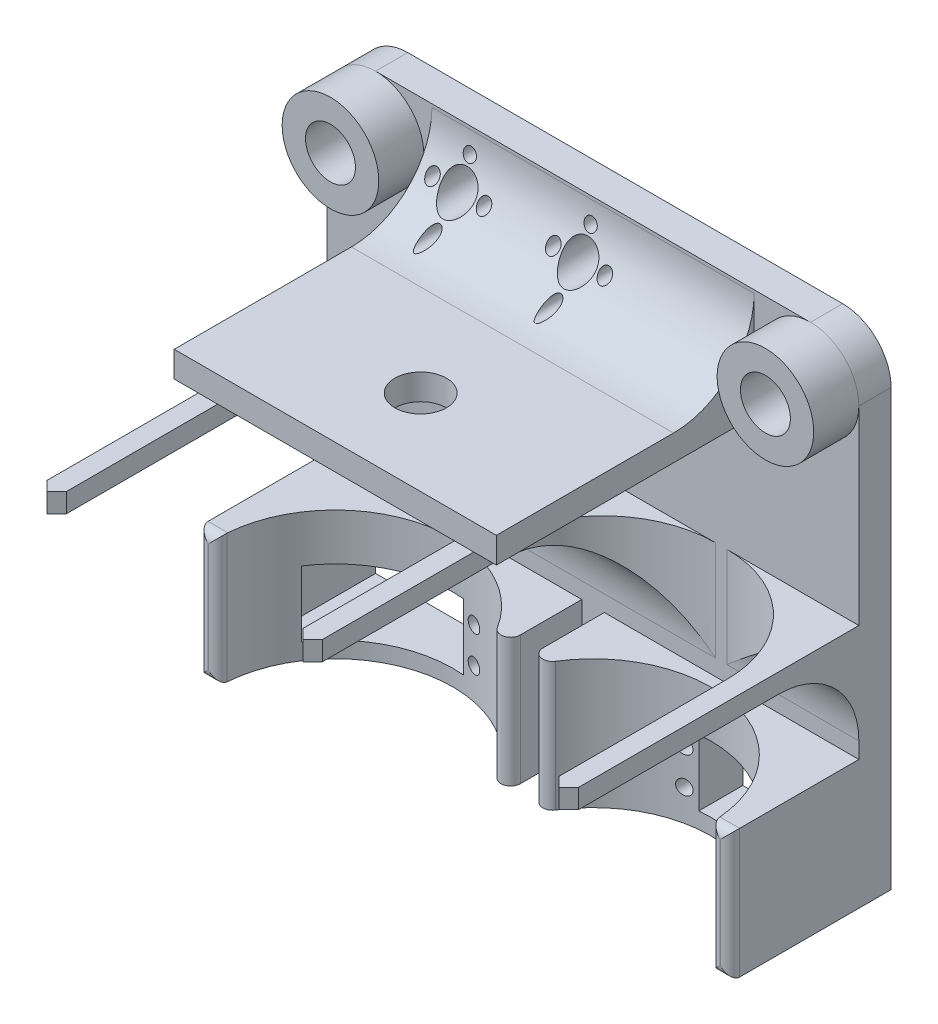
SolidWorks part; units mm, degrees
ref_plane "Plan de face" through (0, 0, 0) normal (0, 0, 1) x (1, 0, 0)
ref_plane "Plan de dessus" through (0, 0, 0) normal (0, 1, 0) x (1, 0, 0)
ref_plane "Plan de droite" through (0, 0, 0) normal (1, 0, 0) x (0, 0, -1)
sketch "Esquisse1" plane through (0, 0, 0) normal (0, 0, 1) x (1, 0, 0)
  line L1 (-82.5, -75) -> (82.5, -75)
  line L2 (-82.5, -75) -> (-82.5, 75)
  line L3 (-82.5, 75) -> (82.5, 75)
  line L4 (82.5, -75) -> (82.5, 75)
  line L5 (-82.5, -75) -> (82.5, 75) construction
  line L6 (-82.5, 75) -> (82.5, -75) construction
  point P0 (0, 0)
  dimension "D1" = 165
  dimension "D2" = 150
extrude "Boss.-Extru.1" add sketch "Esquisse1" along normal blind 10
sketch "Esquisse2" plane through (0, 0, 10) normal (0, 0, 1) x (1, 0, 0)
  line L0 (-82.5, 75) -> (-82.5, -75) construction
  line L1 (82.5, 75) -> (-82.5, 75) construction
  line L2 (0, -55) -> (0, 55) construction
  circle A0 centre (-67.5, 60) radius 7.75
  circle A2 centre (67.5, 60) radius 7.75
  dimension "D1" = 15.5
  dimension "D3" = 15
  dimension "D2" = 15
extrude "Enlèv. mat.-Extru.1" cut sketch "Esquisse2" against normal blind 10
sketch "Esquisse3" plane through (0, 0, 0) normal (0, 0, -1) x (-1, 0, 0)
  circle A0 centre (-67.5, 60) radius 15
  circle A1 centre (67.5, 60) radius 15
  circle A2 centre (-67.5, 60) radius 7.75
  circle A3 centre (67.5, 60) radius 7.75
  dimension "D1" = 30
  dimension "D2" = 30
extrude "Boss.-Extru.2" add sketch "Esquisse3" against normal blind 24
fillet "Congé1" radius 15 2 edges at (82.5, 75, 5) (-82.5, 75, 5)
sketch "Esquisse4" plane through (0, 0, 0) normal (0, 0, -1) x (-1, 0, 0)
  line L0 (-67.5, 75) -> (67.5, 75) construction
  line L1 (82.5, 60) -> (82.5, -75) construction
  circle A0 centre (0, 60) radius 5.25
  circle A1 centre (0, 60) radius 11
  circle A2 centre (0, 52) radius 2
  circle A3 centre (-8, 60) radius 2
  circle A4 centre (0, 68) radius 2
  circle A5 centre (8, 60) radius 2
  circle A6 centre (37.5, 60) radius 5.25
  circle A7 centre (37.5, 60) radius 11
  circle A8 centre (37.5, 52) radius 2
  circle A9 centre (29.5, 60) radius 2
  circle A10 centre (37.5, 68) radius 2
  circle A11 centre (45.5, 60) radius 2
  point P18 (0, 60)
  point P26 (37.5, 60)
  point P32 (42.5, 60)
  point P33 (37.5, 60)
  dimension "D1" = 10.5
  dimension "D2" = 15
  dimension "D3" = 10.5
  dimension "D4" = 22
  dimension "D5" = 4
  dimension "D6" = 8
  dimension "D8" = 22
  dimension "D9" = 4
  dimension "D10" = 8
  dimension "D11" = 45
  dimension "D12" = 15
  dimension "D7" = 4
  dimension "D13" = 4
extrude "Enlèv. mat.-Extru.2" cut sketch "Esquisse4" against normal blind 28 contours A6 | A9 | A10 | A11 | A8 | A2 | A5 | A4 | A3 | A0 region at (-37.5, 60, 0) region at (-37.5, 52, 0) region at (-29.5, 60, 0) region at (-37.5, 68, 0) region at (-45.5, 60, 0)
sketch "Esquisse6" plane through (0, -75, 0) normal (0, -1, 0) x (1, 0, 0)
  line L0 (-82.5, 10) -> (82.5, 10) construction
  line L2 (-76.5, 10) -> (-3.5, 10)
  line L3 (-3.5, 10) -> (-3.5, 50)
  line L4 (0, 0) -> (0, 41.8553) construction
  line L5 (3.5, 10) -> (3.5, 50)
  line L6 (76.5, 10) -> (3.5, 10)
  line L8 (-52.5, 10) -> (-82.5, 10) construction
  line L10 (-82.5, 10) -> (-82.5, 50)
  line L11 (-82.5, 50) -> (-76.5, 50)
  line L12 (-82.5, 10) -> (-76.5, 10)
  line L13 (76.5, 10) -> (82.5, 10)
  line L14 (82.5, 10) -> (82.5, 50)
  line L15 (82.5, 50) -> (76.5, 50)
  arc A0 (-76.5, 50) -> (-3.5, 50) centre (-40, 50) ccw
  arc A1 (76.5, 50) -> (3.5, 50) centre (40, 50) cw
  dimension "D1" = 36.5
  dimension "D2" = 73
  dimension "D3" = 40
  dimension "D4" = 6
extrude "Boss.-Extru.3" add sketch "Esquisse6" against normal blind 40
sketch "Esquisse5" plane through (0, 0, 0) normal (0, 0, -1) x (-1, 0, 0)
  line L0 (-82.5, -75) -> (-82.5, 60) construction
  line L1 (-77.5, -70) -> (-36.5, -70)
  line L2 (-77.5, -70) -> (-77.5, -49.5)
  line L3 (-77.5, -49.5) -> (-36.5, -49.5)
  line L4 (-36.5, -70) -> (-36.5, -49.5)
  line L5 (82.5, -75) -> (-82.5, -75) construction
  line L6 (0, 13.2) -> (0, -13.2) construction
  line L7 (36.5, -70) -> (36.5, -49.5)
  line L8 (77.5, -70) -> (36.5, -70)
  line L9 (77.5, -70) -> (77.5, -49.5)
  line L10 (77.5, -49.5) -> (36.5, -49.5)
  line L11 (-77.5, -59.75) -> (-36.5, -59.75) construction
  circle A0 centre (-32.65, -54.25) radius 2.25
  circle A2 centre (-32.65, -65.25) radius 2.25
  circle A3 centre (32.65, -65.25) radius 2.25
  circle A4 centre (32.65, -54.25) radius 2.25
  dimension "D5" = 4.5
  dimension "D6" = 4.75
  dimension "D1" = 41
  dimension "D2" = 20.5
  dimension "D3" = 5
  dimension "D4" = 5
  dimension "D8" = 3.85
extrude "Enlèv. mat.-Extru.3" cut sketch "Esquisse5" against normal blind 30
sketch "Esquisse8" plane through (0, 0, 10) normal (0, 0, 1) x (1, 0, 0)
  line L0 (67.5, 75) -> (-67.5, 75) construction
  line L1 (-50, 41) -> (50, 41)
  line L2 (-50, 41) -> (-50, 49)
  line L3 (-50, 49) -> (50, 49)
  line L4 (50, 41) -> (50, 49)
  line L5 (-50, 41) -> (50, 49) construction
  line L6 (-50, 49) -> (50, 41) construction
  point P0 (0, 45)
  dimension "D1" = 8
  dimension "D2" = 100
  dimension "D3" = 30
extrude "Boss.-Extru.4" add sketch "Esquisse8" along normal blind 80
sketch "Esquisse9" plane through (0, 0, 10) normal (0, 0, 1) x (1, 0, 0)
  line L0 (-82.5, 60) -> (-82.5, -35) construction
  line L1 (-82.5, -5) -> (-76.5, -5)
  line L2 (-82.5, -5) -> (-82.5, 1)
  line L3 (-82.5, 1) -> (-76.5, 1)
  line L4 (-76.5, -5) -> (-76.5, 1)
  line L5 (-82.5, -5) -> (-76.5, 1) construction
  line L6 (-82.5, 1) -> (-76.5, -5) construction
  line L7 (-50, 41) -> (50, 41) construction
  line L8 (0, 25.5214) -> (0, 7.1933) construction
  line L9 (82.5, 1) -> (76.5, -5) construction
  line L10 (82.5, -5) -> (76.5, 1) construction
  line L11 (76.5, -5) -> (76.5, 1)
  line L12 (82.5, 1) -> (76.5, 1)
  line L13 (82.5, -5) -> (82.5, 1)
  line L14 (82.5, -5) -> (76.5, -5)
  line L16 (3, 1) -> (-3, 1)
  line L17 (3, 1) -> (3, -5)
  line L18 (3, -5) -> (-3, -5)
  line L19 (-3, 1) -> (-3, -5)
  line L20 (3, 1) -> (-3, -5) construction
  line L21 (3, -5) -> (-3, 1) construction
  point P0 (-79.5, -2)
  point P16 (79.5, -2)
  point P24 (0, -2)
  dimension "D1" = 6
  dimension "D2" = 6
  dimension "D3" = 0
  dimension "D4" = 40
  dimension "D5" = 6
  dimension "D6" = 6
extrude "Boss.-Extru.5" add sketch "Esquisse9" along normal blind 90
fillet "Congé2" radius 35 4 edges at (3, -2, 10) (-76.5, -2, 10) (76.5, -2, 10) (-3, -2, 10)
sketch "Esquisse10" plane through (0, 49, 0) normal (0, 1, 0) x (1, 0, 0)
  line L0 (-40, -50) -> (63.4141, -50) construction
  line L1 (0, -50) -> (0, -13.5) construction
  line L2 (0, -13.5) -> (0, -63.5) construction
  circle A1 centre (0, -63.5) radius 8
  dimension "D3" = 16
  dimension "D1" = 36.5
  dimension "D2" = 50
extrude "Enlèv. mat.-Extru.5" cut sketch "Esquisse10" against normal blind 35
chamfer "Chanfrein1" distance 3 angle 45 6 edges at (76.5, -2, 100) (82.5, -2, 100) (-3, -2, 100) (3, -2, 100) (-82.5, -2, 100) (-76.5, -2, 100)
fillet "Congé3" radius 25 3 edges at (62, -5, 10) (0, -5, 10) (-62, -5, 10)
fillet "Congé4" radius 25 1 edges at (0, 49, 10)
fillet "Congé5" radius 3 10 edges at (76.5, -55, 50) (79.5, -35, 50) (82.5, -55, 50) (79.5, -75, 50) (-82.5, -55, 50) (-79.5, -35, 50) (-76.5, -55, 50) (-79.5, -75, 50) (3.5, -55, 50) (-3.5, -55, 50)
